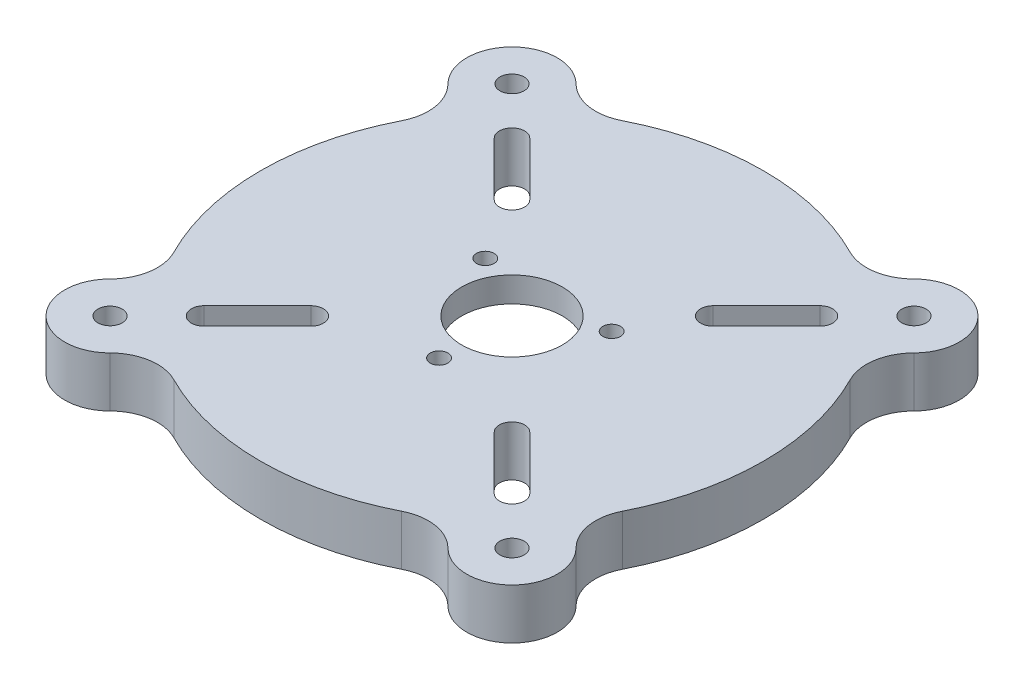
SolidWorks part; units mm, degrees
ref_plane "Front Plane" through (0, 0, 0) normal (0, 0, 1) x (1, 0, 0)
ref_plane "Top Plane" through (0, 0, 0) normal (0, 1, 0) x (1, 0, 0)
ref_plane "Right Plane" through (0, 0, 0) normal (1, 0, 0) x (0, 0, -1)
sketch "Sketch1" plane through (0, 0, 0) normal (0, 1, 0) x (1, 0, 0)
  line L0 (-39.9515, -39.9515) -> (39.9515, 39.9515) construction
  line L1 (-46.3155, -33.5876) -> (33.5876, 46.3155) construction
  line L2 (-33.5876, -46.3155) -> (46.3155, 33.5876) construction
  line L3 (0, 0) -> (0, 50) construction
  line L4 (-39.9515, 39.9515) -> (39.9515, -39.9515) construction
  line L5 (-33.5876, 46.3155) -> (46.3155, -33.5876) construction
  line L6 (-46.3155, 33.5876) -> (33.5876, -46.3155) construction
  line L7 (39.9515, 39.9515) -> (-39.9515, -39.9515) construction
  line L8 (46.3155, 33.5876) -> (-33.5876, -46.3155) construction
  line L9 (33.5876, 46.3155) -> (-46.3155, -33.5876) construction
  line L10 (39.9515, -39.9515) -> (-39.9515, 39.9515) construction
  line L11 (33.5876, -46.3155) -> (-46.3155, 33.5876) construction
  line L12 (46.3155, -33.5876) -> (-33.5876, 46.3155) construction
  line L13 (20, 20) -> (30.6066, 30.6066) construction
  line L14 (18.2322, 21.7678) -> (28.8388, 32.3744)
  line L15 (21.7678, 18.2322) -> (32.3744, 28.8388)
  line L16 (20, -20) -> (30.6066, -30.6066) construction
  line L17 (21.7678, -18.2322) -> (32.3744, -28.8388)
  line L18 (18.2322, -21.7678) -> (28.8388, -32.3744)
  line L19 (-20, -20) -> (-30.6066, -30.6066) construction
  line L20 (-18.2322, -21.7678) -> (-28.8388, -32.3744)
  line L21 (-21.7678, -18.2322) -> (-32.3744, -28.8388)
  line L22 (-20, 20) -> (-30.6066, 30.6066) construction
  line L23 (-21.7678, 18.2322) -> (-32.3744, 28.8388)
  line L24 (-18.2322, 21.7678) -> (-28.8388, 32.3744)
  circle A0 centre (0, 0) radius 50
  arc A1 (-46.3155, -33.5876) -> (-33.5876, -46.3155) centre (-39.9515, -39.9515) ccw construction
  arc A2 (46.3155, 33.5876) -> (33.5876, 46.3155) centre (39.9515, 39.9515) ccw construction
  arc A3 (-33.5876, 46.3155) -> (-46.3155, 33.5876) centre (-39.9515, 39.9515) ccw construction
  arc A4 (33.5876, -46.3155) -> (46.3155, -33.5876) centre (39.9515, -39.9515) ccw construction
  arc A5 (46.3155, 33.5876) -> (33.5876, 46.3155) centre (39.9515, 39.9515) ccw construction
  arc A6 (-46.3155, -33.5876) -> (-33.5876, -46.3155) centre (-39.9515, -39.9515) ccw construction
  arc A7 (33.5876, -46.3155) -> (46.3155, -33.5876) centre (39.9515, -39.9515) ccw construction
  arc A8 (-33.5876, 46.3155) -> (-46.3155, 33.5876) centre (-39.9515, 39.9515) ccw construction
  arc A9 (22.6482, 44.5764) -> (33.5876, 46.3155) centre (26.9196, 52.9834) ccw
  arc A10 (46.3155, 33.5876) -> (44.5764, 22.6482) centre (52.9834, 26.9196) ccw
  arc A11 (18.2322, 21.7678) -> (21.7678, 18.2322) centre (20, 20) ccw
  arc A12 (32.3744, 28.8388) -> (28.8388, 32.3744) centre (30.6066, 30.6066) ccw
  circle A13 centre (39.9515, 39.9515) radius 2.4
  arc A14 (33.5876, 46.3155) -> (46.3155, 33.5876) centre (39.9515, 39.9515) cw
  circle A15 centre (39.9515, -39.9515) radius 2.4
  arc A16 (44.5764, -22.6482) -> (46.3155, -33.5876) centre (52.9834, -26.9196) ccw
  arc A17 (46.3155, -33.5876) -> (33.5876, -46.3155) centre (39.9515, -39.9515) cw
  arc A18 (33.5876, -46.3155) -> (22.6482, -44.5764) centre (26.9196, -52.9834) ccw
  arc A19 (21.7678, -18.2322) -> (18.2322, -21.7678) centre (20, -20) ccw
  arc A20 (28.8388, -32.3744) -> (32.3744, -28.8388) centre (30.6066, -30.6066) ccw
  circle A21 centre (-39.9515, -39.9515) radius 2.4
  arc A22 (-22.6482, -44.5764) -> (-33.5876, -46.3155) centre (-26.9196, -52.9834) ccw
  arc A23 (-33.5876, -46.3155) -> (-46.3155, -33.5876) centre (-39.9515, -39.9515) cw
  arc A24 (-46.3155, -33.5876) -> (-44.5764, -22.6482) centre (-52.9834, -26.9196) ccw
  arc A25 (-18.2322, -21.7678) -> (-21.7678, -18.2322) centre (-20, -20) ccw
  arc A26 (-32.3744, -28.8388) -> (-28.8388, -32.3744) centre (-30.6066, -30.6066) ccw
  circle A27 centre (-39.9515, 39.9515) radius 2.4
  arc A28 (-44.5764, 22.6482) -> (-46.3155, 33.5876) centre (-52.9834, 26.9196) ccw
  arc A29 (-46.3155, 33.5876) -> (-33.5876, 46.3155) centre (-39.9515, 39.9515) cw
  arc A30 (-33.5876, 46.3155) -> (-22.6482, 44.5764) centre (-26.9196, 52.9834) ccw
  arc A31 (-21.7678, 18.2322) -> (-18.2322, 21.7678) centre (-20, 20) ccw
  arc A32 (-28.8388, 32.3744) -> (-32.3744, 28.8388) centre (-30.6066, 30.6066) ccw
  point P5 (0, 0)
  point P16 (0, 0)
  point P23 (0, 0)
  point P30 (0, 0)
  point P40 (25.3033, 25.3033)
  point P59 (25.3033, -25.3033)
  point P75 (-25.3033, -25.3033)
  point P91 (-25.3033, 25.3033)
  dimension "D1" = 100
  dimension "D2" = 20
  dimension "D6" = 2.5
  dimension "D9" = 4.8
  dimension "D10" = 9
  dimension "D12" = 20
  dimension "D3" = 113
  dimension "D4" = 45
  dimension "D7" = 15
  dimension "D8" = 20
  dimension "D11" = 20
  dimension "D5" = 4
extrude "Boss-Extrude2" add sketch "Sketch1" along normal blind 10 contours A0 A32 L24 A31 L23 A26 L21 A25 L20 A20 L18 A19 L17 A12 L15 A11 L14 | A30 A29 A28 A0 A27 | A24 A23 A22 A0 A21 | A18 A17 A16 A0 A15 | A14 A9 A0 A10 A13 region at (0, 0, 0) region at (35.6184, 0, -35.6184) region at (43.3031, 0, 28.4586) region at (-35.6184, 0, -35.6184) region at (-28.4586, 0, 43.3031)
sketch "Sketch2" plane through (0, 0, 0) normal (0, -1, 0) x (1, 0, 0)
  circle A0 centre (0, 0) radius 21.25
  circle A1 centre (0, 14.5) radius 1.75
  circle A2 centre (12.5574, -7.25) radius 1.75
  circle A3 centre (-12.5574, -7.25) radius 1.75
  circle A4 centre (0, 0) radius 10
  dimension "D1" = 42.5
  dimension "D3" = 3.5
  dimension "D6" = 20
  dimension "D2" = 14.5
  dimension "D4" = 3
  dimension "D5" = 21.0302
extrude "Cut-Extrude3" cut sketch "Sketch2" against normal blind 5
extrude "Cut-Extrude4" cut sketch "Sketch2<2>" against normal through all contours A4 | A3 | A1 | A2 region at (0, 0, 0)
sketch "Sketch2<2>" plane through (0, 0, 0) normal (0, -1, 0) x (1, 0, 0) same geometry as "Sketch2"
